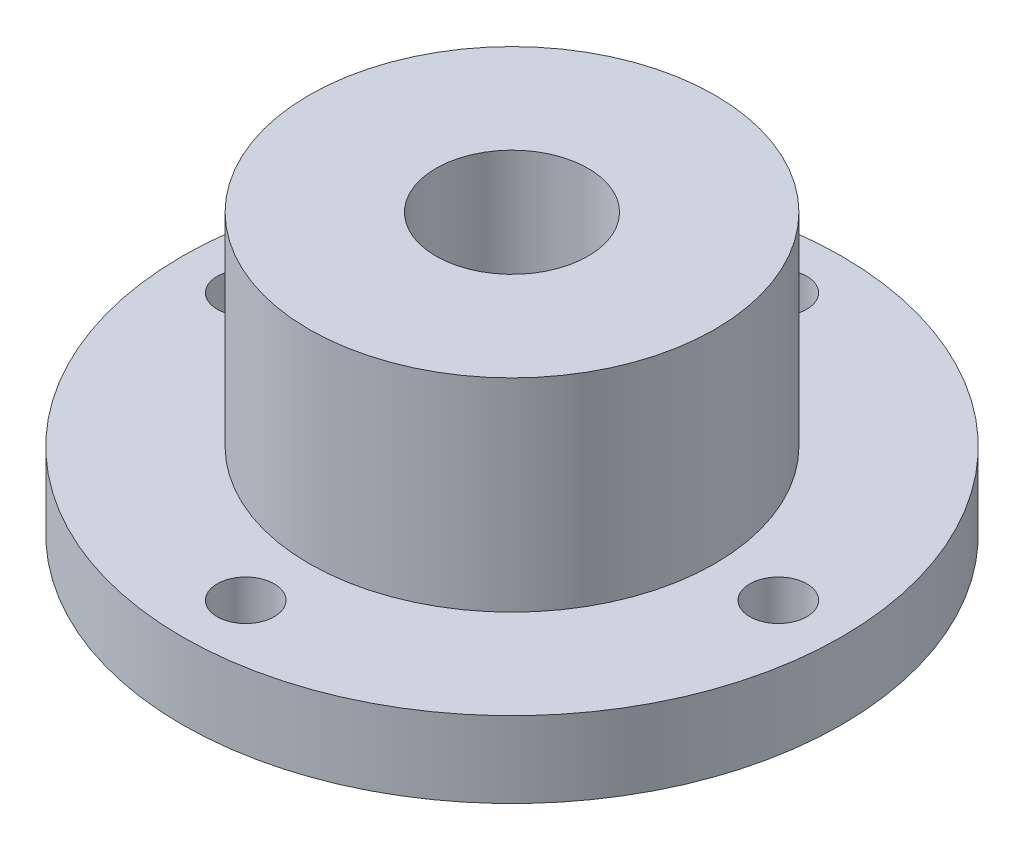
SolidWorks part; units mm, degrees
material "3.0205 (EN-AW 1200)"
ref_plane "前视基准面" through (0, 0, 0) normal (0, 0, 1) x (1, 0, 0)
ref_plane "上视基准面" through (0, 0, 0) normal (0, 1, 0) x (1, 0, 0)
ref_plane "右视基准面" through (0, 0, 0) normal (1, 0, 0) x (0, 0, -1)
sketch "草图1" plane through (0, 0, 0) normal (0, 1, 0) x (1, 0, 0)
  line L0 (-21.3601, 0) -> (22.3582, 0) construction
  line L1 (0, 0) -> (0, 19.5135) construction
  circle A0 centre (0, 0) radius 26
  circle A1 centre (0, 0) radius 16
  circle A2 centre (0, 0) radius 6
  circle A3 centre (-21, 0) radius 2.25
  circle A4 centre (0, 21) radius 2.25
  circle A5 centre (21, 0) radius 2.25
  circle A6 centre (0, -21) radius 2.25
  point P8 (21, 0)
  point P10 (-21, 0)
  point P11 (0, 21)
  point P12 (0, -21)
  point P21 (0, 0)
  point P22 (0, 0)
  point P23 (0, 0)
  point P24 (0, 0)
  point P25 (0, 0)
  point P26 (0, 0)
  point P27 (0, 0)
  dimension "D1" = 52
  dimension "D2" = 32
  dimension "D3" = 12
  dimension "D4" = 4.5
  dimension "D5" = 4.5
  dimension "D6" = 4.5
  dimension "D7" = 4.5
extrude "凸台-拉伸1" add sketch "草图1" along normal blind 6 contours A0 A6 A5 A4 A3 A1 region at (-25.2646, 0, 0)
extrude "凸台-拉伸2" add sketch "草图1<6>" along normal blind 22 contours A1 A2 region at (-15.5475, 0, 0)
sketch "草图1<6>" plane through (0, 0, 0) normal (0, 1, 0) x (1, 0, 0) same geometry as "草图1"
